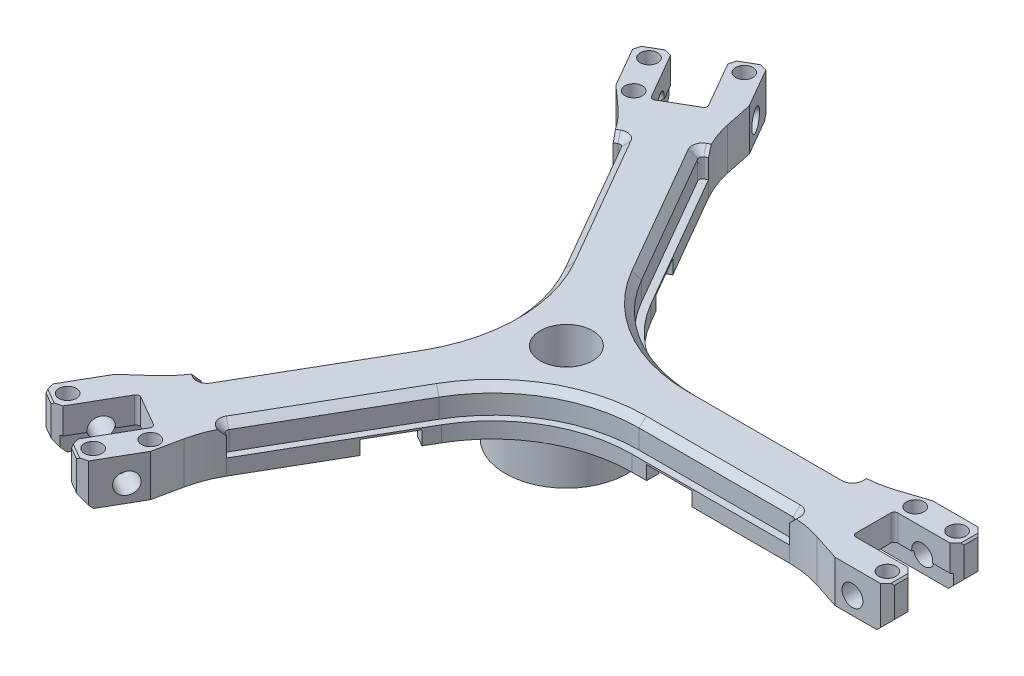
SolidWorks part; units mm, degrees
material "6061"
ref_plane "Front" through (0, 0, 0) normal (0, 0, 1) x (1, 0, 0)
ref_plane "Top" through (0, 0, 0) normal (0, 1, 0) x (1, 0, 0)
ref_plane "Right" through (0, 0, 0) normal (1, 0, 0) x (0, 0, -1)
sketch "Sketch12" plane through (0, 0, 0) normal (0, 0, 1) x (1, 0, 0)
  line L0 (0, -4.1755) -> (0, 46.4371) construction
  line L2 (0, 0) -> (17.5, 0)
  line L3 (0, 0) -> (0, 11)
  line L4 (0, 11) -> (17.5, 11)
  line L5 (17.5, 0) -> (17.5, 11)
  dimension "D1" = 35
  dimension "D2" = 11
revolve "Revolve1" add sketch "Sketch12" angle 360 about L0
sketch "Sketch2" plane through (0, 11, 0) normal (0, 1, 0) x (1, 0, 0)
  line L0 (-7.1488, 0) -> (113.6354, 0) construction
  line L1 (0, 0) -> (5.7735, 10)
  line L2 (5.7735, 10) -> (74, 10)
  line L3 (0, 0) -> (5.7735, -10)
  line L4 (5.7735, -10) -> (74, -10)
  line L5 (88, 6) -> (106, 6)
  line L6 (106, 6) -> (106, 14)
  line L7 (106, 14) -> (91, 14)
  line L8 (91, 14) -> (83.3383, 11.4904)
  line L9 (88, -6) -> (106, -6)
  line L10 (106, -6) -> (106, -14)
  line L11 (106, -14) -> (91, -14)
  line L12 (91, -14) -> (83.3383, -11.4904)
  line L13 (88, 6) -> (88, -6)
  arc A0 (74, 10) -> (83.3383, 11.4904) centre (74, 40) ccw
  arc A1 (83.3383, -11.4904) -> (74, -10) centre (74, -40) ccw
  dimension "D3" = 60
  dimension "D1" = 28
  dimension "D2" = 106
  dimension "D4" = 88
  dimension "D5" = 120
  dimension "D6" = 12
  dimension "D7" = 20
  dimension "D8" = 15
  dimension "D9" = 74
extrude "Boss-Extrude1" add sketch "Sketch2" along normal blind 12
pattern_circular "CirPattern1" count 3 over 360 about axis through (0, -4.1755, 0) along (0, -1, 0) of "Boss-Extrude1" reverse direction yes
fillet "Fillet1" radius 40 3 edges at (-11.547, 17, 0) (5.7735, 17, -10) (5.7735, 17, 10)
sketch "Sketch4" plane through (0, 23, 0) normal (0, 1, 0) x (1, 0, 0)
  line L2 (-28.3397, -69.0859) -> (-5.7735, -30) construction
  line L3 (28.8675, -10) -> (74, -10) construction
  line L4 (-28.3397, -69.0859) -> (-5.7735, -30)
  line L5 (28.8675, -10) -> (74, -10)
  line L6 (-30.0718, -68.0859) -> (-7.5056, -29)
  line L7 (28.8675, -8) -> (74, -8)
  line L8 (74, -8) -> (74, -10)
  line L9 (-30.0718, -68.0859) -> (-28.3397, -69.0859)
  arc A1 (28.8675, -10) -> (-5.7735, -30) centre (28.8675, -50) ccw construction
  arc A2 (28.8675, -10) -> (-5.7735, -30) centre (28.8675, -50) ccw
  arc A3 (28.8675, -8) -> (-7.5056, -29) centre (28.8675, -50) ccw
  dimension "D1" = 2
extrude "Cut-Extrude1" cut sketch "Sketch4" against normal blind 7.5
pattern_circular "CirPattern2" count 3 over 360 about axis through (0, -4.1755, 0) along (0, -1, 0) of "Cut-Extrude1" reverse direction yes
sketch "Sketch5" plane through (0, 11, 0) normal (0, -1, 0) x (1, 0, 0)
  line L0 (-8.657, 0) -> (130.237, 0) construction
  line L1 (26.5, 6.5) -> (106, 6.5)
  line L3 (26.5, -6.5) -> (106, -6.5)
  line L4 (106, 6.5) -> (106, -6.5)
  line L5 (106, -6) -> (106, -14) construction
  arc A0 (26.5, 6.5) -> (26.5, -6.5) centre (26.5, 0) ccw
  dimension "D1" = 13
  dimension "D2" = 20
extrude "Cut-Extrude2" cut sketch "Sketch5" against normal blind 4.5
pattern_circular "CirPattern3" count 3 over 360 about axis through (0, -4.1755, 0) along (0, -1, 0) of "Cut-Extrude2" reverse direction yes
sketch "Sketch6" plane through (0, 0, 0) normal (0, 0, 1) x (1, 0, 0)
  line L0 (0, 25.4424) -> (0, -3.7714) construction
  line L1 (0, 0) -> (0, 23)
  line L3 (0, 23) -> (7.5, 23)
  line L4 (7.5, 23) -> (7.5, 12.5)
  line L5 (7.5, 12.5) -> (5, 12.5)
  line L6 (5, 12.5) -> (5, 4.5)
  line L7 (5, 4.5) -> (7.5, 4.5)
  line L8 (7.5, 4.5) -> (7.5, 0)
  line L10 (7.5, 0) -> (0, 0)
  line L11 (28.8675, 23) -> (-7.5056, 23) construction
  line L13 (-17.5, 0) -> (17.5, 0) construction
  dimension "D1" = 15
  dimension "D2" = 10
  dimension "D3" = 4.5
  dimension "D4" = 8
revolve "Cut-Revolve1" cut sketch "Sketch6" angle 360 about L0
sketch "Sketch7" plane through (0, 0, 0) normal (0, 0, 1) x (1, 0, 0)
  circle A0 centre (96, 16) radius 3
  dimension "D1" = 6
  dimension "D2" = 96
  dimension "D3" = 16
extrude "Cut-Extrude3" cut sketch "Sketch7" against normal through all and the other way through all
pattern_circular "CirPattern4" count 3 over 360 about axis through (0, -4.1755, 0) along (0, -1, 0) of "Cut-Extrude3" reverse direction yes
sketch "Sketch13" plane through (0, 0, 0) normal (0, -1, 0) x (1, 0, 0)
  line L0 (-1.7764, 0) -> (16.1931, 0) construction
  line L2 (4.899, 1) -> (9.5, 1)
  line L3 (4.899, 1) -> (4.899, -1)
  line L4 (4.899, -1) -> (9.5, -1)
  line L5 (9.5, 1) -> (9.5, -1)
  circle A2 centre (0, 0) radius 5 construction
  dimension "D1" = 2
  dimension "D2" = 9.5
extrude "Cut-Extrude4" cut sketch "Sketch13" against normal blind 6.8
sketch "Sketch8" plane through (0, 23, 0) normal (0, 1, 0) x (1, 0, 0)
  line L0 (-20.3316, 0) -> (119.0483, 0) construction
  circle A0 centre (102, -10) radius 2.5
  circle A1 centre (102, 10) radius 2.5
  circle A2 centre (90, 10) radius 2.5
  dimension "D1" = 5
  dimension "D2" = 102
  dimension "D3" = 20
  dimension "D4" = 90
extrude "Cut-Extrude5" cut sketch "Sketch8" against normal blind 5
pattern_circular "CirPattern5" count 3 over 360 about axis through (0, -4.1755, 0) along (0, -1, 0) of "Cut-Extrude5" reverse direction yes
sketch "Sketch9a" plane through (0, 0, 0) normal (0, 0, 1) x (1, 0, 0)
  line L0 (28.8675, 11) -> (74, 11) construction
  line L1 (33, 11) -> (46, 11)
  line L2 (33, 11) -> (33, 15)
  line L3 (33, 15) -> (46, 15)
  line L4 (46, 11) -> (46, 15)
  line L5 (0, -1.6555) -> (0, 26.2269) construction
  dimension "D1" = 33
  dimension "D2" = 13
  dimension "D3" = 4
extrude "Cut-Extrude6" cut sketch "Sketch9a" against normal through all and the other way through all
pattern_circular "CirPattern6" count 3 over 360 about axis through (0, -4.1755, 0) along (0, -1, 0) of "Cut-Extrude6"
hole_wizard "M4x0.7 Tapped Hole1" positions "Sketch11" profile "Sketch10" tap size "M4x0.7" standard "JIS" end condition through all
sketch "Sketch11" plane through (0, 18, 0) normal (0, 1, 0) x (-1, 0, 0)
  point P0 (-102, 10)
  point P1 (-102, -10)
  point P7 (-90, -10)
sketch "Sketch10" plane through (102, 18, 10) normal (1, 0, 0) x (0, 0, 1)
  line L0 (0, 0) -> (0, 18)
  line L1 (0, 18) -> (1.65, 18)
  line L2 (1.65, 18) -> (1.65, 0)
  line L5 (1.65, 0) -> (0, 0)
  line L11 (0, -6.35) -> (0, 107.95) construction
  dimension "Thru Tap Drill Dia." = 3.3
  dimension "Thru Tap Drill Depth" = 18
cosmetic thread "Hole Thread1" parameters "D2"=4
cosmetic thread "Hole Thread2" parameters "D2"=4
cosmetic thread "Hole Thread3" parameters "D2"=4
pattern_circular "CirPattern7" count 3 over 360 about axis through (0, -4.1755, 0) along (0, -1, 0) of "M4x0.7 Tapped Hole1" reverse direction yes
fillet "Fillet2" radius 1 14 edges at (9.5, 3.4, -1) (9.5, 3.4, 1) (74, 19.25, 8) (-38.8038, 19.25, 79.2102) (-49.1962, 19.25, 73.2102) (-30.0718, 19.25, 68.0859) (-43.9282, 19.25, 60.0859) (-43.9282, 19.25, -60.0859) (-49.1962, 19.25, -73.2102) (-38.8038, 19.25, -79.2102) (-30.0718, 19.25, -68.0859) (74, 19.25, -8) (88, 19.25, 6) (88, 19.25, -6)
chamfer "Chamfer1" distance 3 angle 45 6 edges at (-44.1232, 11, 96.9237) (-61.8768, 11, 86.6737) (-44.1232, 11, -96.9237) (-61.8768, 11, -86.6737) (106, 11, -10.25) (106, 11, 10.25)
chamfer "Chamfer2" distance 2 angle 45 33 edges at (-65.1244, 18.5, -84.7987) (-58.1962, 19.25, -88.7987) (-47.8038, 19.25, -94.7987) (-40.8756, 18.5, -98.7987) (-40.8756, 18.5, 98.7987) (-47.8038, 19.25, 94.7987) (-58.1962, 19.25, 88.7987) (-65.1244, 18.5, 84.7987) (106, 18.5, -14) (106, 19.25, -6) (106, 19.25, 6) (106, 18.5, 14) (74, 23, -9.5) (-28.7728, 23, -68.8359) (73.7071, 23, -8.2929) (-29.6717, 23, -67.9787) (50.9338, 23, -8) (7.8675, 23, -13.6269) (-18.5387, 23, -48.1099) (-45.2272, 23, -59.3359) (-45.2272, 23, 59.3359) (-44.0354, 23, -59.6858) (-44.0354, 23, 59.6858) (-32.3951, 23, -40.1099) (-15.735, 23, 0) (-32.3951, 23, 40.1099) (-28.7728, 23, 68.8359) (74, 23, 9.5) (-29.6717, 23, 67.9787) (73.7071, 23, 8.2929) (-18.5387, 23, 48.1099) (7.8675, 23, 13.6269) (50.9338, 23, 8)
chamfer "Chamfer3" distance 1 angle 45 1 edges at (-7.5, 0, 0)
chamfer "Chamfer4" distance 0.5 angle 45 6 edges at (-44.3397, 23, -96.7987) (-61.6603, 23, -86.7987) (-44.3397, 23, 96.7987) (-61.6603, 23, 86.7987) (106, 23, -10) (106, 23, 10)
